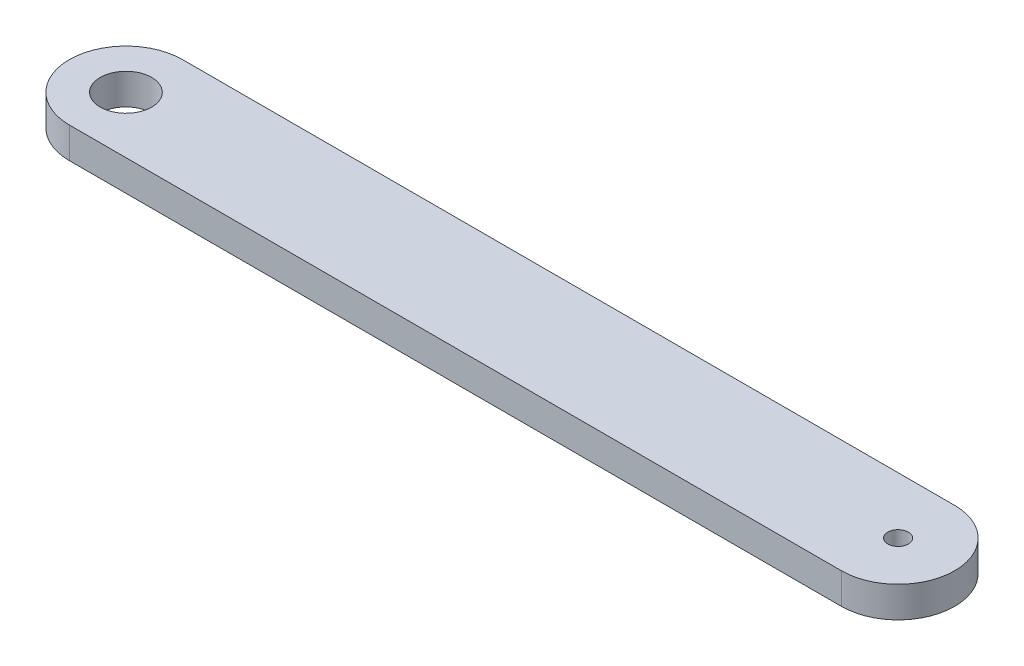
SolidWorks part; units mm, degrees
ref_plane "Front Plane" through (0, 0, 0) normal (0, 0, 1) x (1, 0, 0)
ref_plane "Top Plane" through (0, 0, 0) normal (0, 1, 0) x (1, 0, 0)
ref_plane "Right Plane" through (0, 0, 0) normal (1, 0, 0) x (0, 0, -1)
sketch "Sketch2" plane through (0, 0, 0) normal (0, 1, 0) x (1, 0, 0)
  line L0 (75, 0) -> (-75, 0) construction
  line L1 (75, -11) -> (-75, -11)
  line L2 (75, 11) -> (-75, 11)
  arc A0 (75, -11) -> (75, 11) centre (75, 0) ccw
  arc A1 (-75, 11) -> (-75, -11) centre (-75, 0) ccw
  circle A2 centre (75, 0) radius 2
  circle A3 centre (-75, 0) radius 5
  point P3 (0, 0)
  dimension "D2" = 11
  dimension "D3" = 10
  dimension "D4" = 4
  dimension "D1" = 150
extrude "Boss-Extrude1" add sketch "Sketch2" along normal blind 6
